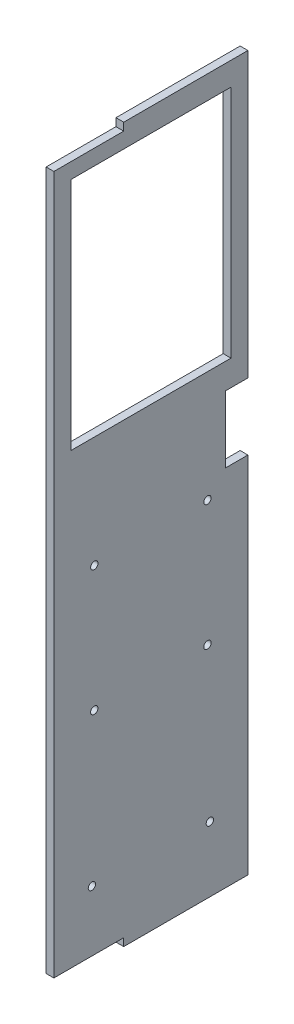
SolidWorks part; units mm, degrees
ref_plane "Front Plane" through (0, 0, 0) normal (0, 0, 1) x (1, 0, 0)
ref_plane "Top Plane" through (0, 0, 0) normal (0, 1, 0) x (1, 0, 0)
ref_plane "Right Plane" through (0, 0, 0) normal (1, 0, 0) x (0, 0, -1)
sketch "Sketch1" plane through (0, 0, 0) normal (1, 0, 0) x (0, 0, -1)
  line L1 (0, 0) -> (79.375, 0)
  line L2 (0, 0) -> (0, 285.75)
  line L3 (0, 285.75) -> (79.375, 285.75)
  line L4 (79.375, 0) -> (79.375, 285.75)
  dimension "D1" = 79.375
  dimension "D2" = 285.75
extrude "Boss-Extrude1" add sketch "Sketch1" along normal blind 3.175
ref_plane "Plane1" through (0, 0, -39.6875) normal (0, 0, -1) x (-1, 0, 0)
sketch "Sketch2" plane through (0, 0, 0) normal (-1, 0, 0) x (0, 0, 1)
  line L1 (-72.4535, 183.388) -> (-6.9215, 183.388)
  line L2 (-72.4535, 183.388) -> (-72.4535, 279.4)
  line L3 (-72.4535, 279.4) -> (-6.9215, 279.4)
  line L4 (-6.9215, 183.388) -> (-6.9215, 279.4)
  line L6 (-79.375, 285.75) -> (0, 285.75) construction
  point P6 (-39.6875, 285.75)
  point P7 (-39.6875, 279.4)
  dimension "D1" = 96.012
  dimension "D2" = 65.532
  dimension "D3" = 6.35
extrude "Cut-Extrude1" cut sketch "Sketch2" against normal up to next
sketch "Sketch3" plane through (0, 0, 0) normal (-1, 0, 0) x (0, 0, 1)
  line L0 (-79.375, 0) -> (-79.375, 285.75) construction
  line L1 (-79.375, 145.605) -> (-70.1675, 145.605)
  line L2 (-79.375, 145.605) -> (-79.375, 172.905)
  line L3 (-79.375, 172.905) -> (-70.1675, 172.905)
  line L4 (-70.1675, 145.605) -> (-70.1675, 172.905)
  line L5 (-65.8175, 172.905) -> (-61.6175, 172.905) construction
  line L6 (-61.6175, 145.605) -> (-59.1175, 145.605) construction
  line L7 (-70.1675, 159.005) -> (-70.1675, 156.505) construction
extrude "Cut-Extrude2" cut sketch "Sketch3" against normal up to next
hole_wizard "Ø3.0mm Dowel Hole1" positions "Sketch4" profile "Sketch5" hole size "Ø3.0" standard "ANSI Metric" end condition up to next
sketch "Sketch4" plane through (0, 0, 0) normal (-1, 0, 0) x (0, 0, 1)
  point P0 (-63.8175, 23.495)
  point P3 (-15.5575, 24.765)
  point P6 (-16.5375, 86.605)
  point P9 (-62.8375, 86.605)
  point P12 (-62.8375, 137.905)
  point P15 (-16.5375, 137.905)
sketch "Sketch5" plane through (0, 23.495, -63.8175) normal (0, 1, 0) x (0, 0, 1)
  line L0 (0, 0) -> (0, 3.175)
  line L1 (0, 3.175) -> (1.5, 3.175)
  line L2 (1.5, 3.175) -> (1.5, 0)
  line L5 (1.5, 0) -> (0, 0)
  line L11 (0, -6.35) -> (0, 107.95) construction
  dimension "Thru Hole Dia." = 3
  dimension "Thru Hole Depth" = 3.175
sketch "Sketch7" plane through (3.175, 0, 0) normal (1, 0, 0) x (0, 0, -1)
  line L1 (79.375, 0) -> (28.575, 0)
  line L2 (79.375, 0) -> (79.375, -3.175)
  line L3 (79.375, -3.175) -> (28.575, -3.175)
  line L4 (28.575, 0) -> (28.575, -3.175)
  line L6 (79.375, 285.75) -> (28.575, 285.75)
  line L7 (79.375, 285.75) -> (79.375, 288.925)
  line L8 (79.375, 288.925) -> (28.575, 288.925)
  line L9 (28.575, 285.75) -> (28.575, 288.925)
  dimension "D1" = 3.175
  dimension "D2" = 3.175
  dimension "D3" = 50.8
extrude "Boss-Extrude2" add sketch "Sketch7" against normal blind 3.175 separate body
combine bodies "Combine1" operation type add bodies to combine 107 105 106
